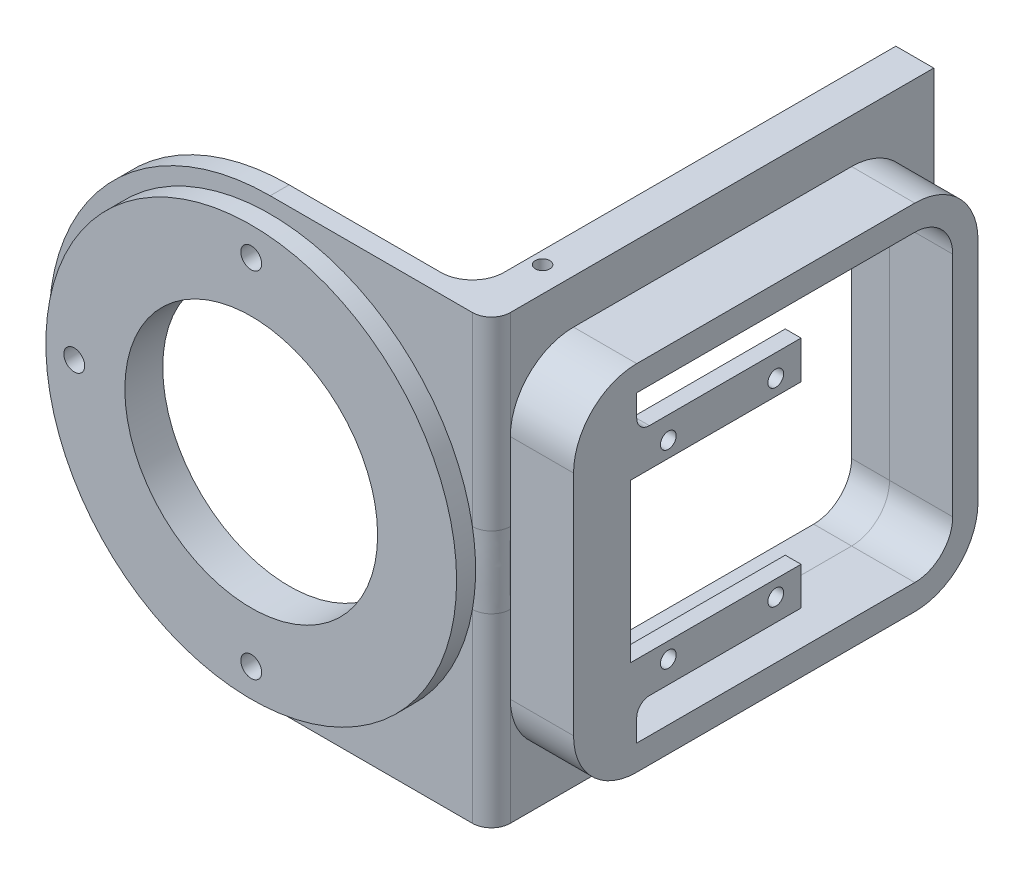
SolidWorks part; units mm, degrees
ref_plane "Front Plane" through (0, 0, 0) normal (0, 0, 1) x (1, 0, 0)
ref_plane "Top Plane" through (0, 0, 0) normal (0, 1, 0) x (1, 0, 0)
ref_plane "Right Plane" through (0, 0, 0) normal (1, 0, 0) x (0, 0, -1)
sketch "Sketch1" plane through (0, 0, 0) normal (0, 0, 1) x (1, 0, 0)
  circle A5 centre (0, 0) radius 32.5
  dimension "D1" = 65
extrude "Boss-Extrude1" add sketch "Sketch1" against normal blind 3
ref_plane "Plane1" through (45, 0, 0) normal (1, 0, 0) x (0, 0, -1)
sketch "Sketch10" plane through (0, 0, -3) normal (0, 0, -1) x (-1, 0, 0)
  line L1 (-35, -35) -> (35, -35)
  line L2 (-35, -35) -> (-35, 35)
  line L3 (-35, 35) -> (35, 35)
  line L4 (35, -35) -> (35, 35)
  line L5 (-35, -35) -> (35, 35) construction
  line L6 (-35, 35) -> (35, -35) construction
  point P0 (0, 0)
  point P5 (0, 0)
  point P6 (0, 0)
  dimension "D1" = 70
  dimension "D2" = 70
extrude "Boss-Extrude6" add sketch "Sketch10" along normal blind 70
sketch "Sketch2" plane through (45, 0, 0) normal (1, 0, 0) x (0, 0, -1)
  line L2 (0, 0) -> (146.6861, 0) construction
  line L3 (38, 0) -> (38, 30) construction
  line L5 (3, 35) -> (3, -35) construction
  line L6 (73, 35) -> (73, -35) construction
  line L7 (16, -28) -> (60, -28)
  line L8 (6, -18) -> (6, 18)
  line L9 (16, 28) -> (60, 28)
  line L10 (70, -18) -> (70, 18)
  line L11 (6, -28) -> (70, 28) construction
  line L12 (6, 28) -> (70, -28) construction
  arc A1 (16, -28) -> (6, -18) centre (16, -18) cw
  arc A2 (60, -28) -> (70, -18) centre (60, -18) ccw
  arc A3 (60, 28) -> (70, 18) centre (60, 18) cw
  arc A4 (6, 18) -> (16, 28) centre (16, 18) cw
  point P0 (73, 0)
  dimension "D1" = 64
  dimension "D3" = 10
  dimension "D2" = 56
extrude "Boss-Extrude2" add sketch "Sketch2" against normal up to surface (10 mm away) separate body up to face at (35, 0, -38)
sketch "Sketch11" plane through (0, 35, 0) normal (0, 1, 0) x (1, 0, 0)
  line L1 (-35, 73) -> (29, 73)
  line L2 (-35, 73) -> (-35, 6)
  line L3 (-35, 6) -> (29, 6)
  line L4 (29, 73) -> (29, 6)
  dimension "D1" = 67
  dimension "D2" = 64
extrude "Cut-Extrude5" cut sketch "Sketch11" against normal through all
sketch "Sketch4" plane through (35, 0, 0) normal (-1, 0, 0) x (0, 0, 1)
  line L8 (-60, -24) -> (-16, -24)
  line L9 (-66, 18) -> (-66, -18)
  line L10 (-16, 24) -> (-60, 24)
  line L11 (-10, -18) -> (-10, 18)
  line L12 (-60, -24) -> (-16, -24)
  line L13 (-66, 18) -> (-66, -18)
  line L14 (-16, 24) -> (-60, 24)
  line L15 (-10, -18) -> (-10, 18)
  arc A10 (-66, -18) -> (-60, -24) centre (-60, -18) ccw
  arc A11 (-60, 24) -> (-66, 18) centre (-60, 18) ccw
  arc A12 (-10, 18) -> (-16, 24) centre (-16, 18) ccw
  arc A13 (-16, -24) -> (-10, -18) centre (-16, -18) ccw
  arc A14 (-66, -18) -> (-60, -24) centre (-60, -18) ccw
  arc A15 (-60, 24) -> (-66, 18) centre (-60, 18) ccw
  arc A16 (-10, 18) -> (-16, 24) centre (-16, 18) ccw
  arc A17 (-16, -24) -> (-10, -18) centre (-16, -18) ccw
  dimension "D1" = 4
extrude "Cut-Extrude2" cut sketch "Sketch4" against normal through all contours L12 A17 L15 A16 L14 A15 L13 A14 region at (35, 0, -38)
sketch "Sketch5" plane through (45, 0, 0) normal (1, 0, 0) x (0, 0, -1)
  line L0 (45, 0) -> (10, 0) construction
  line L1 (42, 18.5) -> (42, 12.5)
  line L2 (42, 12.5) -> (15, 12.5)
  line L3 (15, 12.5) -> (15, -12.5)
  line L4 (15, -12.5) -> (42, -12.5)
  line L5 (42, -12.5) -> (42, -18.5)
  line L6 (42, -18.5) -> (16, -18.5)
  line L8 (42, 18.5) -> (16, 18.5)
  line L10 (45, 0) -> (45, -15) construction
  line L11 (45, -15) -> (38, -15) construction
  line L12 (38, -15) -> (35, -15) construction
  line L13 (35, -15) -> (21, -15) construction
  line L15 (10, 18) -> (10, -18)
  line L16 (16, 18.5) -> (16, 24)
  line L17 (16, -18.5) -> (16, -24)
  line L18 (10, -18) -> (10, 18) construction
  circle A0 centre (45, 0) radius 11 construction
  arc A1 (16, 24) -> (10, 18) centre (16, 18) ccw construction
  circle A2 centre (38, -15) radius 1.25
  arc A3 (16, 24) -> (10, 18) centre (16, 18) ccw
  circle A6 centre (21, -15) radius 1.25
  circle A7 centre (38, 15) radius 1.25
  circle A9 centre (21, 15) radius 1.25
  arc A10 (10, -18) -> (16, -24) centre (16, -18) ccw
  point P8 (15, 0)
  dimension "D1" = 22
  dimension "D6" = 2.5
  dimension "D3" = 25
  dimension "D4" = 15
  dimension "D5" = 7
  dimension "D7" = 17
  dimension "D9" = 6
  dimension "D10" = 5
  dimension "D12" = 3
  dimension "D2" = 30
extrude "Boss-Extrude3" add sketch "Sketch5" against normal blind 2.5
sketch "Sketch13" plane through (35, 0, 0) normal (1, 0, 0) x (0, 0, -1)
  line L4 (10, 18) -> (10, -18)
  line L5 (16, -24) -> (60, -24)
  line L6 (66, -18) -> (66, 18)
  line L7 (60, 24) -> (16, 24)
  line L8 (10, 18) -> (10, -18)
  line L9 (16, -24) -> (60, -24)
  line L10 (66, -18) -> (66, 18)
  line L11 (60, 24) -> (16, 24)
  arc A6 (16, 24) -> (10, 18) centre (16, 18) ccw
  arc A7 (10, -18) -> (16, -24) centre (16, -18) ccw
  arc A8 (60, -24) -> (66, -18) centre (60, -18) ccw
  arc A9 (66, 18) -> (60, 24) centre (60, 18) ccw
  arc A10 (16, 24) -> (10, 18) centre (16, 18) ccw
  arc A11 (10, -18) -> (16, -24) centre (16, -18) ccw
  arc A12 (60, -24) -> (66, -18) centre (60, -18) ccw
  arc A13 (66, 18) -> (60, 24) centre (60, 18) ccw
  dimension "D1" = 0
extrude "Cut-Extrude6" cut sketch "Sketch13" against normal up to surface (6 mm away) up to face at (29, 0, -39.5)
sketch "Sketch14" plane through (0, 0, 0) normal (0, 0, 1) x (1, 0, 0)
  line L0 (29, 35) -> (-35, -35) construction
  line L2 (29, -35) -> (29, 35) construction
  line L3 (29, -35) -> (29, 35) construction
  circle A2 centre (0, 0) radius 32.5
  circle A3 centre (0, 0) radius 28.5
  circle A4 centre (0, 0) radius 32.5 construction
  point P0 (-3.8321, 2.607)
  point P3 (-30.8429, -44.3276)
  point P5 (0, 0)
  point P7 (0, 0)
  point P8 (0, 0)
  point P11 (29.6447, 37)
  dimension "D1" = 0
sketch "Sketch16" plane through (45, 0, 0) normal (1, 0, 0) x (0, 0, -1)
  circle A0 centre (38, -15) radius 2.25
  circle A2 centre (21, -15) radius 2.25
  circle A3 centre (21, 15) radius 2.25
  circle A5 centre (38, 15) radius 2.25
  dimension "D1" = 4.5
extrude "Cut-Extrude8" [suppressed] cut sketch "Sketch16" against normal blind 2.5
fillet "Fillet1" radius 3 1 edges at (35, 0, -3)
fillet "Fillet2" [suppressed] radius 10
sketch "Sketch17" plane through (0, 0, -6) normal (0, 0, -1) x (-1, 0, 0)
  line L0 (-28, 0) -> (0, 0) construction
  line L1 (0, 28) -> (0, 0) construction
  line L2 (28, 0) -> (0, 0) construction
  line L3 (0, -28) -> (0, 0) construction
  circle A0 centre (-28, 0) radius 1.65 construction
  circle A1 centre (0, 28) radius 1.65
  circle A2 centre (28, 0) radius 1.65
  circle A3 centre (0, -28) radius 1.65
  circle A5 centre (0, 0) radius 28.5
  circle A6 centre (0, 0) radius 28.5 construction
  point P2 (6.3748, -2.8846)
  point P10 (0, 0)
  point P17 (0, 0)
  point P19 (0, 0)
  dimension "D4" = 3.3
  dimension "D3" = 28
  dimension "D5" = 0
  dimension "D1" = 4
  dimension "D2" = 4
extrude "Cut-Extrude9" cut sketch "Sketch17" against normal through all
sketch "Sketch19" plane through (29, 0, 0) normal (-1, 0, 0) x (0, 0, 1)
  line L0 (-67, 35) -> (-67, -35) construction
  line L1 (-6, 35) -> (-73, 35) construction
  line L2 (-6, -35) -> (-73, -35) construction
  line L3 (-73, -35) -> (-73, 35) construction
  line L4 (-67, 28) -> (-69, 28)
  line L5 (-67, 28) -> (-67, 23.8)
  line L6 (-67, 23.8) -> (-69, 23.8)
  line L7 (-69, 28) -> (-69, 23.8)
  line L8 (-67, -23.8) -> (-69, -23.8)
  line L9 (-67, -23.8) -> (-67, -28)
  line L10 (-67, -28) -> (-69, -28)
  line L11 (-69, -23.8) -> (-69, -28)
  line L12 (-67, 0) -> (-73, 0) construction
  dimension "D1" = 6
  dimension "D2" = 7
  dimension "D3" = 2
  dimension "D4" = 4.2
extrude "Cut-Extrude10" cut sketch "Sketch19" along direction (1, 0, 0) on the side against the normal blind 4
sketch "Sketch21" plane through (0, 0, -6) normal (0, 0, -1) x (-1, 0, 0)
  line L0 (29, 35) -> (29, -35) construction
  line L1 (31, 28) -> (29, 28)
  line L2 (31, 28) -> (31, 23.8)
  line L3 (31, 23.8) -> (29, 23.8)
  line L4 (29, 28) -> (29, 23.8)
  line L5 (31, -23.8) -> (29, -23.8)
  line L6 (31, -23.8) -> (31, -28)
  line L7 (31, -28) -> (29, -28)
  line L8 (29, -23.8) -> (29, -28)
  line L9 (29, 0) -> (35, 0) construction
  line L10 (35, -35) -> (35, 35) construction
  line L11 (35, 35) -> (-29, 35) construction
  dimension "D1" = 2
  dimension "D2" = 4.2
  dimension "D3" = 7
  dimension "D4" = 6
extrude "Cut-Extrude11" cut sketch "Sketch21" against normal blind 4
sketch "Sketch22" plane through (0, 0, -73) normal (0, 0, -1) x (-1, 0, 0)
  line L0 (-29, 28) -> (-33, 23.8) construction
  line L1 (-29, -23.8) -> (-33, -28) construction
  line L4 (-29, 23.8) -> (-29, 28)
  line L5 (-29, 28) -> (-33, 28)
  line L6 (-33, 28) -> (-33, 23.8)
  line L7 (-33, 23.8) -> (-29, 23.8)
  line L8 (-29, 23.8) -> (-29, 28) construction
  line L9 (-29, 28) -> (-33, 28) construction
  line L11 (-33, 23.8) -> (-29, 23.8) construction
  line L12 (-29, -28) -> (-29, -23.8)
  line L13 (-29, -23.8) -> (-33, -23.8)
  line L14 (-33, -23.8) -> (-33, -28)
  line L15 (-33, -28) -> (-29, -28)
  line L16 (-29, -28) -> (-29, -23.8) construction
  line L17 (-29, -23.8) -> (-33, -23.8) construction
  line L19 (-33, -28) -> (-29, -28) construction
  line L22 (-33, 28) -> (-33, 23.8)
  line L23 (-33, -23.8) -> (-33, -28)
  circle A0 centre (-31, 25.9) radius 1.15
  circle A1 centre (-31, -25.9) radius 1.15
  dimension "D3" = 2.3
  dimension "D1" = 0
  dimension "D2" = 0
extrude "Cut-Extrude12" cut sketch "Sketch22" against normal up to surface (4 mm away) contours A0 | A1 region at (31, 25.9, -73) region at (31, -25.9, -73) up to face at (31, 25.9, -69)
sketch "Sketch23" plane through (-35, 0, 0) normal (-1, 0, 0) x (0, 0, 1)
  line L0 (-6, -28) -> (-3, -23.8) construction
  line L1 (-6, 23.8) -> (-3, 28) construction
  line L4 (-6, -23.8) -> (-6, -28)
  line L5 (-6, -28) -> (-3, -28)
  line L6 (-3, -28) -> (-3, -23.8)
  line L7 (-3, -23.8) -> (-6, -23.8)
  line L8 (-6, -23.8) -> (-6, -28) construction
  line L9 (-6, -28) -> (-3, -28) construction
  line L11 (-3, -23.8) -> (-6, -23.8) construction
  line L12 (-6, 28) -> (-6, 23.8)
  line L13 (-6, 23.8) -> (-3, 23.8)
  line L14 (-3, 23.8) -> (-3, 28)
  line L15 (-3, 28) -> (-6, 28)
  line L16 (-6, 28) -> (-6, 23.8) construction
  line L17 (-6, 23.8) -> (-3, 23.8) construction
  line L19 (-3, 28) -> (-6, 28) construction
  line L22 (-3, -28) -> (-3, -23.8)
  line L23 (-3, 23.8) -> (-3, 28)
  circle A0 centre (-4.5, -25.9) radius 1.15
  circle A1 centre (-4.5, 25.9) radius 1.15
  dimension "D3" = 2.3
  dimension "D1" = 0
  dimension "D2" = 0
sketch "Sketch24" plane through (0, 0, -6) normal (0, 0, -1) x (-1, 0, 0)
  circle A0 centre (0, 0) radius 20
  circle A2 centre (0, 0) radius 28.5
  circle A3 centre (0, 0) radius 28.5 construction
  point P3 (0, 0)
  point P4 (3.7791, -3)
  dimension "D1" = 40
  dimension "D2" = 0
extrude "Cut-Extrude14" cut sketch "Sketch24" against normal up to surface (6 mm away) up to face at (-1.65, 28, 0)
fillet "Fillet4" radius 5 1 edges at (29, 0, -6)
fillet "Fillet5" radius 2 2 edges at (43.75, -18.5, -16) (43.75, 18.5, -16)
fillet "Fillet6" radius 35 2 edges at (-35, -35, -4.5) (-35, 35, -4.5)
sketch "Sketch25" plane through (29, 0, 19) normal (-1, 0, 0) x (0, 0, 1)
  line L1 (-36.2, -29) -> (-36.2, -31)
  line L2 (-36.2, -29) -> (-32, -29)
  line L3 (-32, -29) -> (-32, -31)
  line L4 (-36.2, -31) -> (-32, -31)
  line L9 (-29, -18) -> (-29, 18) construction
  line L11 (-92, -35) -> (-25, -35) construction
  dimension "D1" = 2
  dimension "D2" = 4.2
  dimension "D3" = 6
  dimension "D4" = 3
extrude "Cut-Extrude15" cut sketch "Sketch25" against normal blind 4
ref_plane "Plane2" through (0, 0, 0) normal (0, -1, 0) x (-1, 0, 0)
sketch "Sketch26" plane through (0, -29, 0) normal (0, -1, 0) x (1, 0, 0)
  line L0 (33, -17.2) -> (29, -13) construction
  circle A0 centre (31, -15.1) radius 1.15
  dimension "D1" = 2.3
extrude "Cut-Extrude16" cut sketch "Sketch26" along normal blind 10
mirror "Mirror1" about plane through (0, 0, 0) normal (0, -1, 0) of "Cut-Extrude15", "Cut-Extrude16"
